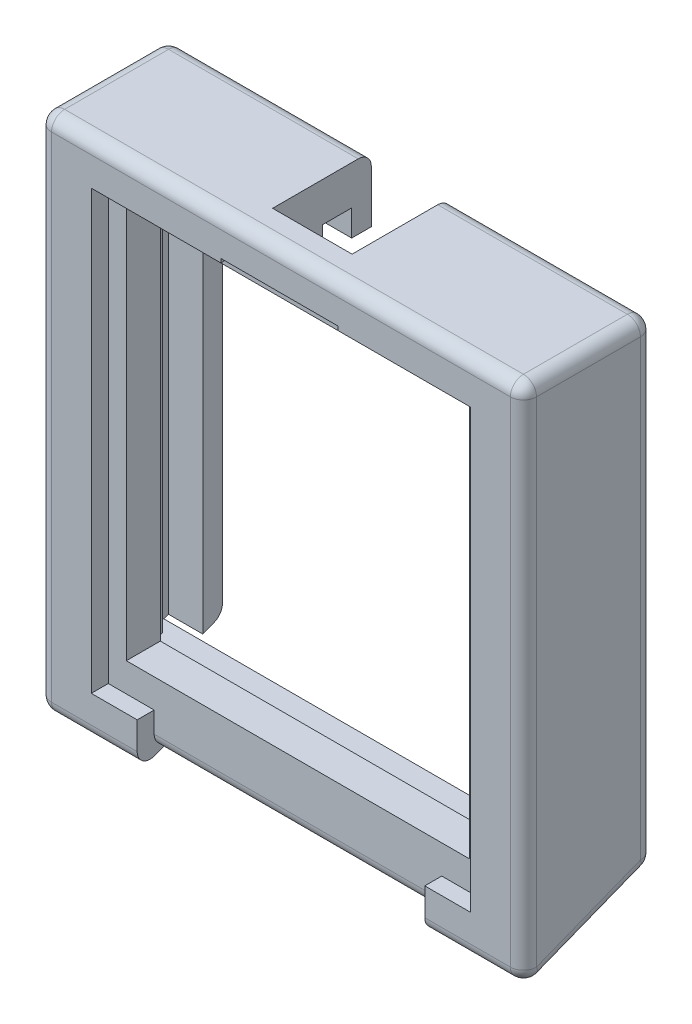
SolidWorks part; units mm, degrees
ref_plane "Front Plane" through (0, 0, 0) normal (0, 0, 1) x (1, 0, 0)
ref_plane "Top Plane" through (0, 0, 0) normal (0, 1, 0) x (1, 0, 0)
ref_plane "Right Plane" through (0, 0, 0) normal (1, 0, 0) x (0, 0, -1)
ref_plane "Plane1" through (0, -10.3522, -4.0632) normal (0, 0.9309, 0.3654) x (1, 0, 0)
ref_plane "Plane2" through (0, 25.1, 0) normal (0, 1, 0) x (1, 0, 0)
sketch "Sketch3" plane through (0, 0, 0) normal (0, 1, 0) x (1, 0, 0)
  line L0 (-14.43, 1.8) -> (-14.43, 0.3)
  line L1 (-14.43, 0.3) -> (-17.05, 0.3)
  line L2 (-17.05, 0.3) -> (-17.05, -1.95)
  line L3 (-17.05, -1.95) -> (-14.27, -1.95)
  line L6 (-14.27, -1.95) -> (-14.27, -3.55)
  line L7 (-14.27, -3.55) -> (-13.13, -3.55)
  line L8 (-13.13, -3.55) -> (-13.13, -6.85)
  line L9 (-13.13, -6.85) -> (-14.51, -6.85)
  line L10 (-14.51, -6.85) -> (-14.51, -8.15)
  line L11 (-14.51, -8.15) -> (-18.55, -8.15)
  line L12 (-18.55, -8.15) -> (-18.55, 1.8)
  line L13 (-18.55, 1.8) -> (-14.43, 1.8)
  line L14 (-15, 0) -> (15, 0) construction
  line L16 (-15, -1.65) -> (15, -1.65) construction
  line L17 (-13.91, -7.15) -> (13.91, -7.15) construction
  line L18 (-13.93, -4.65) -> (-13.93, -6.15) construction
  line L19 (-13.91, -8.65) -> (-13.91, -7.15) construction
  line L20 (-13.91, -8.65) -> (13.91, -8.65) construction
  line L21 (0, 0) -> (0, -15.6727) construction
  line L22 (18.55, 1.8) -> (14.43, 1.8)
  line L23 (18.55, -8.15) -> (18.55, 1.8)
  line L24 (14.51, -8.15) -> (18.55, -8.15)
  line L25 (14.51, -6.85) -> (14.51, -8.15)
  line L26 (13.13, -6.85) -> (14.51, -6.85)
  line L27 (13.13, -3.55) -> (13.13, -6.85)
  line L28 (14.27, -3.55) -> (13.13, -3.55)
  line L29 (14.27, -1.95) -> (14.27, -3.55)
  line L30 (17.05, -1.95) -> (14.27, -1.95)
  line L31 (17.05, 0.3) -> (17.05, -1.95)
  line L32 (14.43, 0.3) -> (17.05, 0.3)
  line L33 (14.43, 1.8) -> (14.43, 0.3)
  line L35 (-16.75, -1.65) -> (-16.75, 0) construction
  line L36 (-13.97, -1.65) -> (-13.97, -3.25) construction
  line L37 (12.446, -3.25) -> (-12.446, -3.25) construction
  dimension "D1" = 0.3
  dimension "D3" = 0.3
  dimension "D8" = 0.3
  dimension "D9" = 0.6
  dimension "D10" = 0.5
  dimension "D11" = 1.5
  dimension "D12" = 1.5
  dimension "D13" = 0.5
  dimension "D4" = 0.8
  dimension "D2" = 0.3
  dimension "D5" = 0.3
  dimension "D6" = 0.3
extrude "Boss-Extrude1" add sketch "Sketch3" along normal up to surface (25.1 mm away) and the other way up to surface up to plane "Plane2" other way up to plane "Plane1"
sketch "Sketch4" plane through (0, 0, 0) normal (1, 0, 0) x (0, 0, -1)
  line L0 (1.8, 25.1) -> (-8.15, 25.1)
  line L1 (-8.15, 25.1) -> (-8.15, 21.9)
  line L2 (-8.15, 25.1) -> (-8.15, -15.1459) construction
  line L3 (-8.15, 21.9) -> (-6.85, 21.9)
  line L4 (-6.85, 25.1) -> (-6.85, -14.6357) construction
  line L5 (-6.85, 21.9) -> (-6.85, 20.6)
  line L6 (-6.85, 20.6) -> (-3.55, 20.6)
  line L7 (-3.55, 25.1) -> (-3.55, -13.3404) construction
  line L8 (-3.55, 20.6) -> (-3.55, 21.02)
  line L9 (-3.55, 25.1) -> (-3.55, -13.3404) construction
  line L11 (-3.55, -10.06) -> (-1.95, -10.06)
  line L14 (1.8, 25.1) -> (1.8, -11.2405) construction
  line L15 (1.8, 22.1) -> (1.8, 25.1)
  line L18 (-1.95, 22.1) -> (0.3, 22.1)
  line L19 (0.3, 22.1) -> (0.3, 20.1)
  line L21 (-1.65, 21.8) -> (0, 21.8) construction
  line L22 (-8.65, -10.97) -> (-7.15, -10.97) construction
  line L23 (-1.95, 25.1) -> (-1.95, -12.7124) construction
  line L24 (-8.15, -11.57) -> (-8.15, -15.1459)
  line L25 (-8.15, -15.1459) -> (-1.95, -12.7124)
  line L26 (-1.95, -12.7124) -> (-1.95, -10.06)
  line L29 (-3.55, -10.06) -> (-3.55, -9.37)
  line L30 (-3.55, -9.37) -> (-6.85, -9.37)
  line L31 (-6.85, -9.37) -> (-6.85, -11.57)
  line L32 (-6.85, 25.1) -> (-6.85, -14.6357) construction
  line L33 (-6.85, -11.57) -> (-8.15, -11.57)
  line L36 (0.3, 25.1) -> (0.3, -11.8293) construction
  line L37 (0.3, 20.1) -> (1.8, 20.1)
  line L38 (1.8, 20.1) -> (1.8, 22.1)
  line L39 (-8.65, 21.3) -> (-7.15, 21.3) construction
  line L40 (-1.65, -9.76) -> (-3.25, -9.76) construction
  line L41 (-3.55, 21.02) -> (-1.95, 21.02)
  line L42 (-1.95, 21.02) -> (-1.95, 22.1)
  line L43 (-1.65, 20.72) -> (-3.25, 20.72) construction
  line L44 (-1.65, 21.8) -> (-1.65, -21.8) construction
  point P42 (-2.45, -9.76)
  dimension "D3" = 0.3
  dimension "D8" = 0.3
  dimension "D2" = 0.3
  dimension "D9" = 2
  dimension "D5" = 0.6
  dimension "D4" = 1.3
  dimension "D1" = 0.6
  dimension "D6" = 1.6
  dimension "D7" = 0.3
extrude "Boss-Extrude2" add sketch "Sketch4" along normal up to surface and the other way up to surface up to face at (18.55, 5.9534, 3.175) other way up to face at (-18.55, 5.9534, 3.175)
fillet "Fillet1" radius 1 2 edges at (0, -12.7124, 1.95) (0, -15.1459, 8.15)
sketch "Sketch5" plane through (0, 0, 8.15) normal (0, 0, 1) x (1, 0, 0)
  line L8 (13.91, -7.47) -> (13.91, 24.8)
  line L9 (13.91, 24.8) -> (4, 24.8)
  line L10 (4, 24.8) -> (4, 25.1)
  line L11 (4, 25.1) -> (-4, 25.1)
  line L12 (-4, 25.1) -> (-4, 24.8)
  line L13 (-4, 24.8) -> (-13.91, 24.8)
  line L14 (-13.91, 24.8) -> (-13.91, -7.47)
  line L15 (-13.91, -7.47) -> (13.91, -7.47)
  line L16 (13.91, -7.47) -> (13.91, 24.8) construction
  line L22 (-13.91, 24.8) -> (-13.91, -7.47) construction
  line L23 (-13.91, -7.47) -> (13.91, -7.47) construction
  line L24 (-11, -11.57) -> (-11, -14.6792)
  line L25 (14.51, -11.57) -> (-14.51, -11.57) construction
  line L26 (-11, -14.6792) -> (11, -14.6792)
  line L27 (-11, -11.57) -> (11, -11.57)
  line L28 (0, 0) -> (0, -15.5564) construction
  line L29 (-10, -7.47) -> (-10, -10.77) construction
  line L30 (-18.55, -14.6792) -> (18.55, -14.6792) construction
  line L31 (11, -11.57) -> (11, -14.6792)
  line L32 (4, 21.6) -> (-4, 21.6) construction
  line L33 (4.3735, 19.9419) -> (-4.6, 19.9419)
  line L34 (4.3735, 19.9419) -> (4.3735, 22.2)
  line L35 (4.3735, 22.2) -> (-4.6, 22.2)
  line L36 (-4.6, 19.9419) -> (-4.6, 22.2)
  line L37 (4.3735, 19.9419) -> (-4.6, 22.2) construction
  line L38 (4.3735, 22.2) -> (-4.6, 19.9419) construction
  line L39 (-4, 21.6) -> (-4, 21.3) construction
  point P2 (-0.1133, 21.071)
  point P30 (0, -11.57)
  point P31 (0, -14.6792)
  dimension "D3" = 1
  dimension "D2" = 0.6
  dimension "D4" = 0.6
extrude "Cut-Extrude1" cut sketch "Sketch5" against normal up to surface (1.3 mm away) up to face at (0, 5.615, 6.85)
chamfer "Chamfer1" distance 0.7 angle 45 4 edges at (0, 20.6, 3.55) (13.13, 5.615, 3.55) (0, -9.37, 3.55) (-13.13, 5.615, 3.55)
fillet "Fillet2" radius 1 15 edges at (-18.55, -12.9253, 2.4923) (-18.55, -14.5054, 7.7133) (18.55, -12.9253, 2.4923) (18.55, -14.5054, 7.7133) (18.55, 25.1, 3.175) (0, 25.1, 8.15) (-18.55, 25.1, 3.175) (0, 25.1, -1.8) (-16.49, -11.2405, -1.8) (16.49, -11.2405, -1.8) (18.55, 6.9297, -1.8) (-18.55, 6.9297, -1.8) (-18.55, 5.7104, 8.15) (18.55, 5.7104, 8.15) (0, -14.6331, 6.85)
sketch "Sketch6" plane through (0, 0, -1.8) normal (0, 0, -1) x (-1, 0, 0)
  line L0 (0, 26.6333) -> (0, 0) construction
  line L1 (3.04, 0.0257) -> (-3.04, 0.0257)
  line L2 (-3.04, 0.0257) -> (-3.04, 25.1)
  line L3 (-3.04, 25.1) -> (3.04, 25.1)
  line L4 (-17.55, 25.1) -> (17.55, 25.1) construction
  line L6 (3.04, 0.0257) -> (3.04, 25.1)
  point P12 (0, 25.1)
  point P13 (0, 0.0257)
  dimension "D1" = 3.04
extrude "Cut-Extrude2" cut sketch "Sketch6" against normal offset from surface (7.55 mm away) 2.5 offset beyond the face yes
chamfer "Chamfer3" distance 1 angle 50 2 edges at (14.27, 5.48, 1.95) (-14.27, 5.48, 1.95) first distance on face at (0, 10.6916, 1.95) first distance on face at (-14.27, 5.48, 2.75)
equation "\"offset\"= .3mm"
equation "\"D1@Sketch3\"=\"offset\""
equation "\"D3@Sketch3\"=\"offset\""
equation "\"D8@Sketch3\"=\"offset\""
equation "\"D9@Sketch3\"=\"offset\"*2"
equation "\"D1@Plane2\"=3+\"offset\""
equation "\"led apnel overlap\"= .8"
equation "\"clearance\"=0.5"
equation "\"D2@Sketch4\"=\"offset\""
equation "\"D2@Sketch5\"=\"offset\"*2"
equation "\"D1@Sketch6\" = .1in + \"clearance\""
equation "\"D2@Sketch3\"=\"offset\""
equation "\"D5@Sketch4\"=\"offset\"*2"
equation "\"D4@Sketch5\"=\"offset\"*2"
equation "\"D1@Sketch4\"=\"offset\"*2"
equation "\"D6@Sketch4\"=1.6"
equation "\"D3@Sketch4\"=\"offset\""
equation "\"D5@Sketch3\"=\"offset\""
equation "\"D6@Sketch3\"=\"offset\""
equation "\"D7@Sketch4\"=\"offset\""
equation "\"D8@Sketch4\"=\"offset\""
